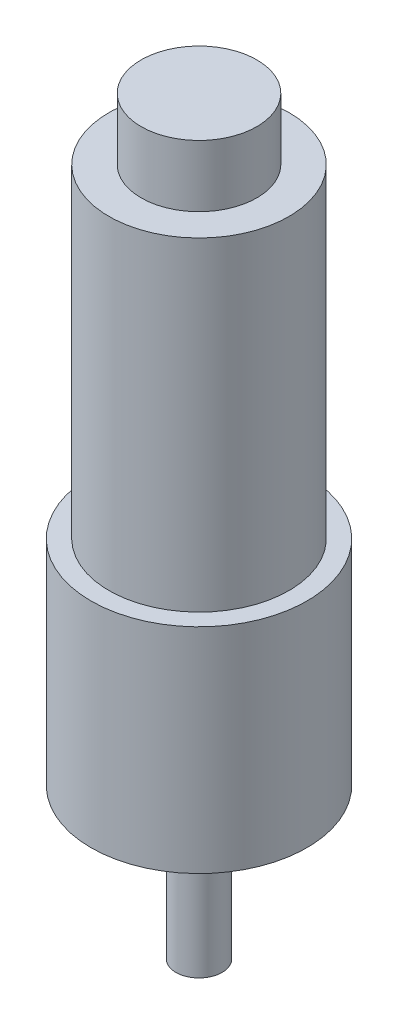
SolidWorks part; units mm, degrees
ref_plane "前视基准面" through (0, 0, 0) normal (0, 0, 1) x (1, 0, 0)
ref_plane "上视基准面" through (0, 0, 0) normal (0, 1, 0) x (1, 0, 0)
ref_plane "右视基准面" through (0, 0, 0) normal (1, 0, 0) x (0, 0, -1)
sketch "草图1" plane through (0, 0, 0) normal (0, 1, 0) x (1, 0, 0)
  circle A0 centre (0, 0) radius 14
  dimension "D1" = 28
extrude "凸台-拉伸1" add sketch "草图1" along normal blind 27.7
sketch "草图3" plane through (0, 27.7, 0) normal (0, 1, 0) x (1, 0, 0)
  circle A1 centre (0, 0) radius 11.6696
extrude "凸台-拉伸2" add sketch "草图3" along normal blind 42
sketch "草图8" plane through (0, 69.7, 0) normal (0, 1, 0) x (1, 0, 0)
  circle A0 centre (0, 0) radius 7.5
  dimension "D1" = 15
extrude "凸台-拉伸4" add sketch "草图8" along normal blind 8
sketch "草图9" plane through (0, 0, 0) normal (0, -1, 0) x (1, 0, 0)
  circle A0 centre (0, 0) radius 8
  dimension "D1" = 16
extrude "凸台-拉伸5" add sketch "草图9" along normal blind 1
sketch "草图5" plane through (0, -1, 0) normal (0, -1, 0) x (1, 0, 0)
  circle A0 centre (0, 0) radius 3
  dimension "D1" = 6
extrude "凸台-拉伸3" add sketch "草图5" along normal blind 18.5
sketch "草图7" plane through (0, -19.5, 0) normal (0, -1, 0) x (1, 0, 0)
  line L0 (-1.6583, -2.5) -> (1.6583, -2.5)
  circle A0 centre (0, 0) radius 3 construction
  arc A1 (-1.6583, -2.5) -> (1.6583, -2.5) centre (0, 0) ccw
  point P5 (0, 3)
  dimension "D1" = 5.5
extrude "切除-拉伸2" cut sketch "草图7" against normal blind 12
sketch "草图4" plane through (0, 0, 0) normal (0, -1, 0) x (1, 0, 0)
  line L0 (0, 0) -> (0, 13.5149) construction
  circle A0 centre (0, 11) radius 1.5
  circle A1 centre (0, 0) radius 11 construction
  circle A2 centre (11, 0) radius 1.5
  circle A3 centre (0, -11) radius 1.5
  circle A4 centre (-11, 0) radius 1.5
  dimension "D1" = 22
  dimension "D2" = 4
  dimension "D3" = 3
extrude "切除-拉伸1" cut sketch "草图4" against normal blind 4
move or copy body "实体-移动/复制1" [suppressed] bodies to move or copy 103
